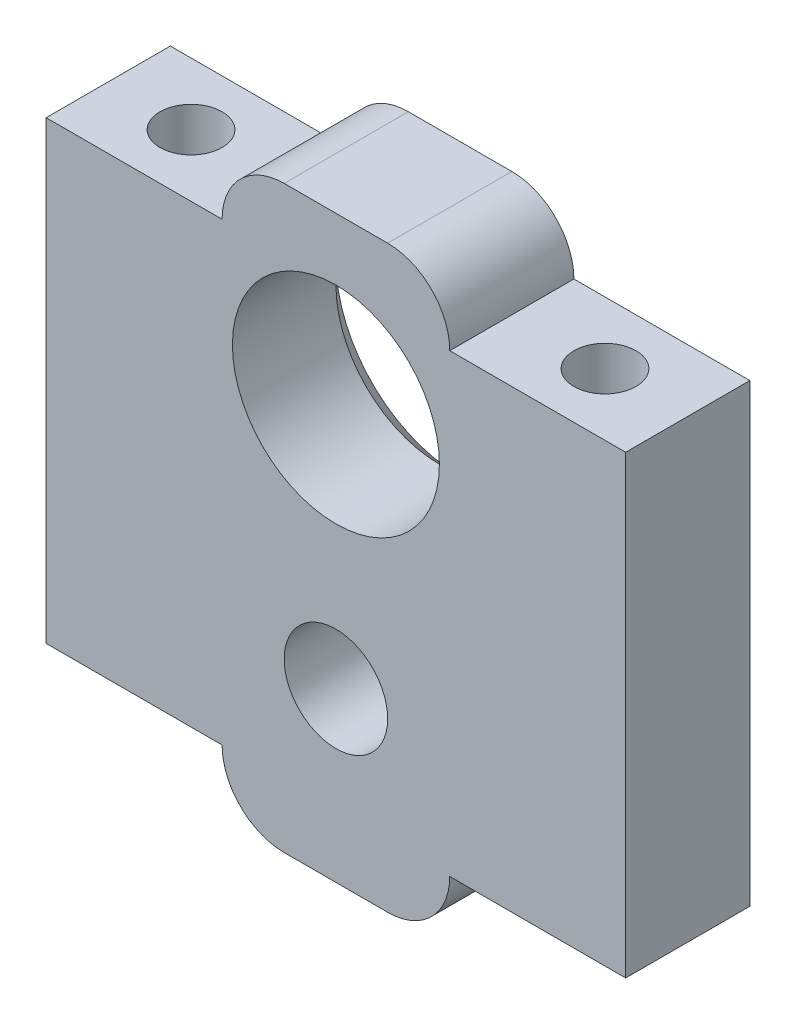
SolidWorks part; units mm, degrees
material "PLA"
ref_plane "前视基准面" through (0, 0, 0) normal (0, 0, 1) x (1, 0, 0)
ref_plane "上视基准面" through (0, 0, 0) normal (0, 1, 0) x (1, 0, 0)
ref_plane "右视基准面" through (0, 0, 0) normal (1, 0, 0) x (0, 0, -1)
sketch "草图1" plane through (0, 0, 0) normal (0, 0, 1) x (1, 0, 0)
  line L1 (14, 14) -> (-14, 14)
  line L2 (14, 14) -> (14, -14)
  line L3 (14, -14) -> (-14, -14)
  line L4 (-14, 14) -> (-14, -14)
  line L5 (14, 14) -> (-14, -14) construction
  line L6 (14, -14) -> (-14, 14) construction
  circle A0 centre (0, -6) radius 2.5
  circle A1 centre (0, 5.9) radius 5
  point P0 (0, 0)
  dimension "D3" = 5
  dimension "D4" = 10
  dimension "D5" = 11.9
  dimension "D1" = 28
  dimension "D2" = 28
  dimension "D6" = 8
extrude "凸台-拉伸1" add sketch "草图1" along normal blind 6
sketch "草图2" plane through (0, -14, 0) normal (0, -1, 0) x (-1, 0, 0)
  line L0 (0, -22.3093) -> (0, 20.8619) construction
  line L1 (14, -6) -> (14, 0) construction
  line L2 (-14, -6) -> (-14, 0) construction
  circle A0 centre (10, -3) radius 1.5
  circle A1 centre (-10, -3) radius 1.5
  point P10 (14, -3)
  point P14 (-14, -3)
  dimension "D1" = 3
  dimension "D2" = 3
  dimension "D3" = 10
  dimension "D4" = 10
extrude "切除-拉伸1" cut sketch "草图2" against normal through all
chamfer "倒角2" distance 1 1 edges at (5, 5.9, 0)
sketch "草图8" plane through (0, 0, 0) normal (0, 0, -1) x (-1, 0, 0)
  line L1 (-14, -14) -> (14, -14)
  line L2 (-14, -14) -> (-14, -14.1)
  line L3 (-14, -14.1) -> (14, -14.1)
  line L4 (14, -14) -> (14, -14.1)
  dimension "D1" = 0.1
  dimension "D2" = 28
extrude "凸台-拉伸4" add sketch "草图8" against normal blind 6
sketch "草图9" plane through (0, 0, 6) normal (0, 0, 1) x (1, 0, 0)
  line L1 (-14, 14) -> (14, 14)
  line L2 (-14, 14) -> (-14, 13.9)
  line L3 (-14, 13.9) -> (14, 13.9)
  line L4 (14, 14) -> (14, 13.9)
  dimension "D1" = 0.1
  dimension "D2" = 28
extrude "切除-拉伸4" cut sketch "草图9" against normal through all
sketch "草图10" plane through (0, 13.9, 0) normal (0, 1, 0) x (1, 0, 0)
  circle A0 centre (-10, -3) radius 1.5
  circle A1 centre (10, -3) radius 1.5
extrude "切除-拉伸5" cut sketch "草图10" against normal through all
sketch "草图11" plane through (0, 13.9, 0) normal (0, 1, 0) x (1, 0, 0)
  line L0 (0, 7.9349) -> (0, -13.571) construction
  line L1 (-5.5, -8) -> (-14.5, -8)
  line L2 (-5.5, -8) -> (-5.5, 2)
  line L3 (-5.5, 2) -> (-14.5, 2)
  line L4 (-14.5, -8) -> (-14.5, 2)
  line L5 (-5.5, -8) -> (-14.5, 2) construction
  line L6 (-5.5, 2) -> (-14.5, -8) construction
  line L7 (5.5, 2) -> (14.5, 2)
  line L8 (14.5, -8) -> (14.5, 2)
  line L9 (5.5, -8) -> (14.5, -8)
  line L10 (5.5, -8) -> (5.5, 2)
  circle A2 centre (-10, -3) radius 1.5
  dimension "D1" = 10
  dimension "D2" = 9
extrude "切除-拉伸6" cut sketch "草图11" against normal blind 3
sketch "草图12" plane through (0, -14.1, 0) normal (0, -1, 0) x (1, 0, 0)
  line L0 (0, 13.1287) -> (0, -6.4418) construction
  line L1 (-14.5, -1.5) -> (-5.5, -1.5)
  line L2 (-14.5, -1.5) -> (-14.5, 7.5)
  line L3 (-14.5, 7.5) -> (-5.5, 7.5)
  line L4 (-5.5, -1.5) -> (-5.5, 7.5)
  line L5 (-14.5, -1.5) -> (-5.5, 7.5) construction
  line L6 (-14.5, 7.5) -> (-5.5, -1.5) construction
  line L7 (14.5, 7.5) -> (5.5, 7.5)
  line L8 (5.5, -1.5) -> (5.5, 7.5)
  line L9 (14.5, -1.5) -> (5.5, -1.5)
  line L10 (14.5, -1.5) -> (14.5, 7.5)
  circle A0 centre (-10, 3) radius 1.5
  dimension "D1" = 9
extrude "切除-拉伸7" cut sketch "草图12" against normal blind 3
fillet "圆角1" radius 3 4 edges at (5.5, -14.1, 3) (-5.5, -14.1, 3) (5.5, 13.9, 3) (-5.5, 13.9, 3)
